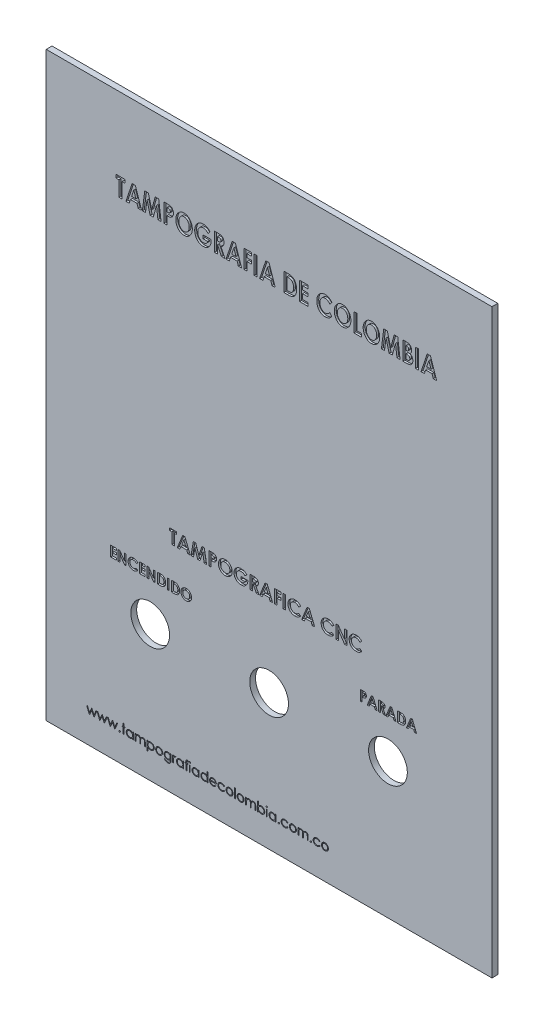
SolidWorks part; units mm, degrees
material "AISI 316 Chapa de acero inoxidable (SS)"
ref_plane "Alzado" through (0, 0, 0) normal (0, 0, 1) x (1, 0, 0)
ref_plane "Planta" through (0, 0, 0) normal (0, 1, 0) x (1, 0, 0)
ref_plane "Vista lateral" through (0, 0, 0) normal (1, 0, 0) x (0, 0, -1)
sketch "Croquis1" plane through (0, 0, 0) normal (0, 0, 1) x (1, 0, 0)
  line L0 (-115, -80) -> (115, -80) construction
  line L1 (115, -150) -> (-115, -150)
  line L2 (115, -150) -> (115, 150)
  line L3 (115, 150) -> (-115, 150)
  line L4 (-115, -150) -> (-115, 150)
  line L5 (115, -150) -> (-115, 150) construction
  line L6 (115, 150) -> (-115, -150) construction
  circle A0 centre (0, -80) radius 10
  circle A1 centre (-61.3333, -80) radius 10
  circle A2 centre (61.3333, -80) radius 10
  point P0 (0, 0)
  dimension "D3" = 20
  dimension "D4" = 20
  dimension "D5" = 20
  dimension "D1" = 300
  dimension "D2" = 230
  dimension "D6" = 70
extrude "Saliente-Extruir1" add sketch "Croquis1" along normal blind 3
sketch "Croquis2" plane through (0, 0, 3) normal (0, 0, 1) x (1, 0, 0)
  line L0 (-85.2953, 102.6702) -> (92.8771, 102.6702) construction
  line L1 (-85.2953, -60.2038) -> (-35.605, -60.2038) construction
  line L2 (46.1226, -60.2038) -> (77.7135, -60.2038) construction
  line L3 (-94.7725, -136.1565) -> (31.5908, -136.1565) construction
  line L4 (-54.9681, -38.8567) -> (54.3362, -38.8567) construction
  text T0 "TAMPOGRAFIA DE COLOMBIA" font "Century Gothic" height in points 36
  text T1 "<b>TAMPOGRAFICA CNC</b>" font "Century Gothic" height in points 26
  text T2 "<b>ENCENDIDO</b>" font "Century Gothic" height in points 20
  text T3 "<b>PARADA</b>" font "Century Gothic" height in points 20
  text T4 "www.tampografiadecolombia.com.co" font "Century Gothic" height in points 18
  point P11 (0, 0)
  point P12 (-88.5555, -61.1382)
  point P13 (-35.605, -60.8267)
  point P14 (-85.2953, -60.2038)
extrude "Cortar-Extruir1" cut sketch "Croquis2" against normal blind 1
